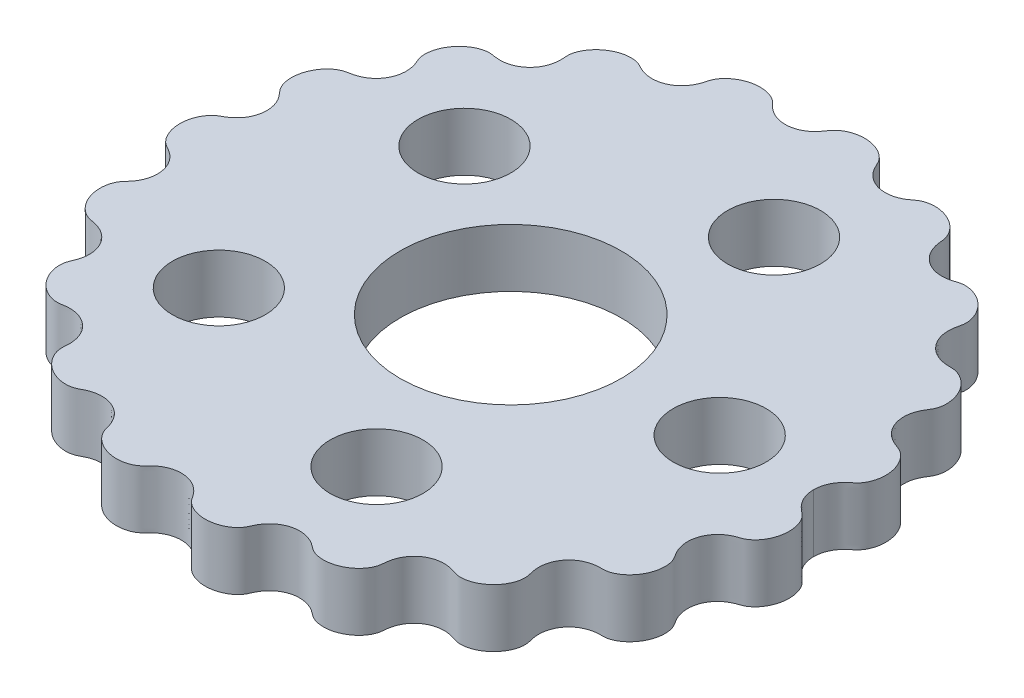
SolidWorks part; units mm, degrees
ref_plane "Front Plane" through (0, 0, 0) normal (0, 0, 1) x (1, 0, 0)
ref_plane "Top Plane" through (0, 0, 0) normal (0, 1, 0) x (1, 0, 0)
ref_plane "Right Plane" through (0, 0, 0) normal (1, 0, 0) x (0, 0, -1)
sketch "Sketch1" plane through (0, 0, 0) normal (0, 1, 0) x (1, 0, 0)
  line L0 (-28.5, 0) -> (26.1, 0) construction
  line L1 (0, 0) -> (-1.2, 0) construction
  line L2 (-1.2, -26.2965) -> (-1.2, 26.2965) construction
  line L3 (0, -27.4748) -> (0, 27.4748) construction
  line L4 (18, 0) -> (16.8, 0)
  line L5 (-1.2, 0) -> (-2.4, 0)
  circle A6 centre (0, 0) radius 9.525
  circle A7 centre (0, 0) radius 18
  circle A8 centre (18, 0) radius 4
  circle A9 centre (5.5623, -17.119) radius 4
  circle A10 centre (-14.5623, -10.5801) radius 4
  circle A11 centre (-14.5623, 10.5801) radius 4
  circle A12 centre (5.5623, 17.119) radius 4
  circle A13 centre (-1.2, 0) radius 30
  circle A14 centre (28.8, 0) radius 2.5
  circle A15 centre (27.3317, -9.2705) radius 2.5
  circle A16 centre (23.0705, -17.6336) radius 2.5
  circle A17 centre (16.4336, -24.2705) radius 2.5
  circle A18 centre (8.0705, -28.5317) radius 2.5
  circle A19 centre (-1.2, -30) radius 2.5
  circle A20 centre (-10.4705, -28.5317) radius 2.5
  circle A21 centre (-18.8336, -24.2705) radius 2.5
  circle A22 centre (-25.4705, -17.6336) radius 2.5
  circle A23 centre (-29.7317, -9.2705) radius 2.5
  circle A24 centre (-31.2, 0) radius 2.5
  circle A25 centre (-29.7317, 9.2705) radius 2.5
  circle A26 centre (-25.4705, 17.6336) radius 2.5
  circle A27 centre (-18.8336, 24.2705) radius 2.5
  circle A28 centre (-10.4705, 28.5317) radius 2.5
  circle A29 centre (-1.2, 30) radius 2.5
  circle A30 centre (8.0705, 28.5317) radius 2.5
  circle A31 centre (16.4336, 24.2705) radius 2.5
  circle A32 centre (23.0705, 17.6336) radius 2.5
  circle A33 centre (27.3317, 9.2705) radius 2.5
  circle A34 centre (-2.4, 0) radius 9.525
  circle A35 centre (-2.4, 0) radius 18
  circle A36 centre (15.6, 0) radius 4
  circle A37 centre (3.1623, -17.119) radius 4
  circle A38 centre (-16.9623, -10.5801) radius 4
  circle A39 centre (-16.9623, 10.5801) radius 4
  circle A40 centre (3.1623, 17.119) radius 4
  spline S0 degree 4 poles (26.9104, 6.6012) (26.9742, 6.5637) (27.0975, 6.4823) (27.3266, 6.2942) (27.6183, 5.9575) (27.8831, 5.5093) (28.0722, 4.9735) (28.1608, 4.4391) (28.1609, 3.9238) (28.093, 3.5007) (27.9838, 3.1507) (27.8591, 2.8784) (27.741, 2.6778) (27.605, 2.4959) (27.4503, 2.337) (27.2759, 2.2009) (27.1019, 2.0648) (26.9367, 1.9177) (26.7821, 1.7596) (26.65, 1.601) (26.5385, 1.4453) (26.4457, 1.295) (26.3692, 1.1524) (26.3017, 1.0053) (26.2435, 0.8544) (26.1947, 0.7002) (26.1557, 0.5423) (26.1271, 0.3877) (26.1084, 0.2314) (26.0989, 0.0495) (26.0994, -0.0671) (26.1108, -0.2691) (26.1342, -0.4315) (26.1693, -0.6042) (26.2157, -0.7717) (26.2733, -0.9361) (26.3418, -1.0961) (26.4279, -1.2656) (26.5348, -1.4419) (26.6997, -1.6703) (26.9014, -1.8899) (27.1248, -2.087) (27.3628, -2.2652) (27.5417, -2.4229) (27.6968, -2.6125) (27.831, -2.8239) (27.9427, -3.0552) (28.032, -3.3021) (28.1133, -3.6202) (28.1642, -4.0114) (28.1582, -4.4659) (28.0687, -4.972) (27.9224, -5.3919) (27.7522, -5.7264) (27.5792, -5.9861) (27.4226, -6.1811) (27.2087, -6.3966) (26.9704, -6.5815) (26.7043, -6.7144) (26.4261, -6.8021) (26.2084, -6.8853) (25.996, -6.9818) (25.7924, -7.0957) (25.5065, -7.2884) (25.1668, -7.5959) (24.8233, -8.0656) (24.5731, -8.7228) (24.5132, -9.3741) (24.5959, -9.9089) (24.7329, -10.3062) (24.8635, -10.5783) (24.9836, -10.7878) (25.1181, -10.988) (25.2439, -11.1944) (25.336, -11.4251) (25.3995, -11.6707) (25.4343, -11.9282) (25.442, -12.1937) (25.4188, -12.5249) (25.3424, -12.9166) (25.1912, -13.3478) (24.9449, -13.7987) (24.6361, -14.1974) (24.3194, -14.493) (24.0146, -14.7042) (23.7442, -14.8441) (23.522, -14.9308) (23.2952, -14.9909) (23.0662, -15.0181) (22.8362, -15.0154) (22.6065, -15.0188) (22.3771, -15.0374) (22.15, -15.0735) (21.9017, -15.1343) (21.6364, -15.2275) (21.2852, -15.3974) (20.867, -15.6962) (20.4577, -16.1544) (20.1676, -16.7441) (20.0407, -17.3441) (20.0443, -17.8376) (20.1013, -18.2083) (20.1783, -18.5102) (20.2374, -18.7529) (20.2542, -19.0071) (20.2367, -19.2645) (20.1753, -19.5877) (20.0454, -19.9662) (19.8257, -20.3791) (19.5033, -20.7922) (19.1257, -21.1406) (18.7061, -21.4192) (18.3126, -21.5978) (17.9573, -21.7007) (17.6591, -21.7472) (17.425, -21.7593) (17.197, -21.746) (16.9781, -21.7045) (16.7675, -21.6331) (16.5576, -21.5612) (16.3432, -21.5027) (16.1253, -21.4593) (15.7965, -21.4204) (15.3549, -21.428) (14.789, -21.5503) (14.1546, -21.8806) (13.6662, -22.3459) (13.3364, -22.8823) (13.1735, -23.3537) (13.1046, -23.717) (13.0767, -24.0228) (13.0578, -24.2682) (12.9987, -24.5141) (12.9032, -24.7542) (12.7442, -25.0453) (12.499, -25.369) (12.1557, -25.6963) (11.7049, -25.9946) (11.2116, -26.2122) (10.69, -26.3437) (10.2213, -26.3776) (9.8206, -26.3426) (9.499, -26.2667) (9.2556, -26.1771) (9.0298, -26.0566) (8.8316, -25.9026) (8.5839, -25.7111) (8.2645, -25.511) (7.8101, -25.3123) (7.2055, -25.1928) (6.5502, -25.2287) (5.9713, -25.4243) (5.5369, -25.6878) (5.2457, -25.9387) (5.0554, -26.1438) (4.8999, -26.3482) (4.7746, -26.5455) (4.6646, -26.7519) (4.569, -26.9649) (4.4763, -27.1796) (4.3535, -27.3793) (4.2033, -27.5619) (4.0321, -27.728) (3.7953, -27.9145) (3.4825, -28.1028) (3.0896, -28.2688) (2.605, -28.3883) (2.0954, -28.4312) (1.5735, -28.39) (1.1195, -28.2728) (0.7516, -28.1124) (0.4728, -27.9399) (0.2735, -27.7809) (0.1002, -27.6012) (-0.0369, -27.4007) (-0.1676, -27.1967) (-0.3131, -27.0024) (-0.5125, -26.7738) (-0.8252, -26.4899) (-1.2868, -26.2024) (-1.9065, -26.0034) (-2.5994, -25.9754) (-3.1568, -26.101) (-3.5653, -26.2832) (-3.8534, -26.4638) (-4.0409, -26.6046) (-4.2161, -26.7602) (-4.3804, -26.9272) (-4.5356, -27.1027) (-4.708, -27.2621) (-4.9066, -27.3955) (-5.1223, -27.5066) (-5.3531, -27.5948) (-5.5951, -27.6608) (-5.9041, -27.715) (-6.2804, -27.7366) (-6.7242, -27.7014) (-7.2225, -27.58) (-7.6392, -27.4035) (-7.9745, -27.2016) (-8.2316, -27.0015) (-8.4208, -26.8224) (-8.5884, -26.628) (-8.73, -26.4192) (-8.8438, -26.1979) (-8.9181, -25.9651) (-8.9731, -25.7277) (-9.0439, -25.4943) (-9.1531, -25.2096) (-9.3068, -24.9159) (-9.5135, -24.6237) (-9.8398, -24.2849) (-10.2644, -23.9778) (-10.8297, -23.7381) (-11.4105, -23.6609) (-11.8763, -23.6964) (-12.2188, -23.7735) (-12.4447, -23.8451) (-12.6638, -23.9353) (-12.8761, -24.0403) (-13.082, -24.1572) (-13.2986, -24.2543) (-13.5339, -24.3178) (-13.7805, -24.3538) (-14.0358, -24.3616) (-14.2964, -24.3431) (-14.6185, -24.2887) (-14.9949, -24.1775) (-15.4086, -23.9883) (-15.8372, -23.7006) (-16.1649, -23.3939) (-16.4043, -23.0978) (-16.5733, -22.8298) (-16.6877, -22.6036) (-16.7767, -22.3723) (-16.8377, -22.1385) (-16.8702, -21.9045) (-16.8664, -21.6745) (-16.8432, -21.4462) (-16.8326, -21.2169) (-16.8373, -20.9873) (-16.8603, -20.7588) (-16.9233, -20.4192) (-17.0718, -19.9806) (-17.369, -19.4772) (-17.8749, -18.9885) (-18.448, -18.6772) (-19.0275, -18.5257) (-19.5101, -18.5038) (-19.8766, -18.5383) (-20.1776, -18.5934) (-20.4214, -18.6224) (-20.6712, -18.6091) (-20.9209, -18.565) (-21.1679, -18.4906) (-21.4096, -18.39) (-21.6982, -18.2354) (-22.0201, -18.0093) (-22.351, -17.6983) (-22.6637, -17.2907) (-22.9048, -16.8434) (-23.0478, -16.4273) (-23.1163, -16.0571) (-23.132, -15.7508) (-23.1187, -15.5137) (-23.0797, -15.2858) (-23.0107, -15.072) (-22.918, -14.8679) (-22.8318, -14.6612) (-22.759, -14.4492) (-22.7023, -14.2323) (-22.658, -13.9823) (-22.6359, -13.6994) (-22.6507, -13.3001) (-22.7619, -12.7838) (-23.0293, -12.2149) (-23.4676, -11.712) (-23.9234, -11.3981) (-24.3155, -11.223) (-24.6094, -11.1314) (-24.8495, -11.076) (-25.0926, -11.0387) (-25.3345, -10.9908) (-25.5693, -10.9005) (-25.7937, -10.7797) (-26.006, -10.6307) (-26.2044, -10.4578) (-26.4303, -10.2184) (-26.6648, -9.8998) (-26.879, -9.4996) (-27.0444, -9.0157) (-27.13, -8.5201) (-27.1345, -8.0871) (-27.0849, -7.7198) (-27.006, -7.4259) (-26.9204, -7.2033) (-26.8122, -6.9952) (-26.6786, -6.8073) (-26.5213, -6.6394) (-26.3676, -6.4686) (-26.2255, -6.2877) (-26.0974, -6.0966) (-25.9747, -5.8762) (-25.8647, -5.6245) (-25.7524, -5.2647) (-25.6818, -4.7626) (-25.731, -4.1469) (-25.9619, -3.524) (-26.3213, -3.0106) (-26.6902, -2.673) (-27.001, -2.4627) (-27.2749, -2.314) (-27.4942, -2.1942) (-27.6938, -2.0358) (-27.8724, -1.8494) (-28.0299, -1.6395) (-28.1658, -1.4106) (-28.2784, -1.1691) (-28.3569, -0.9499) (-28.4099, -0.7574) (-28.4448, -0.5945) (-28.4671, -0.4646) (-28.4838, -0.3341) (-28.4949, -0.1942) (-28.5004, -0.0525) (-28.5005, 0.0456) (-28.4955, 0.1802) (-28.4857, 0.3127) (-28.4674, 0.4669) (-28.4356, 0.6491) (-28.3841, 0.8627) (-28.3055, 1.0987) (-28.2068, 1.3282) (-28.0876, 1.5473) (-27.9509, 1.7495) (-27.7973, 1.9316) (-27.6281, 2.0918) (-27.4431, 2.2241) (-27.2427, 2.3305) (-27.0445, 2.4404) (-26.8537, 2.5632) (-26.6725, 2.6998) (-26.4853, 2.8663) (-26.2987, 3.0673) (-26.073, 3.3712) (-25.8526, 3.7999) (-25.7033, 4.3429) (-25.6908, 4.9349) (-25.7972, 5.4631) (-25.983, 5.9142) (-26.1842, 6.2409) (-26.3898, 6.4964) (-26.5384, 6.6564) (-26.611, 6.7378) (-26.647, 6.7788) knots 0 0 0 0 0 0.002514 0.005029 0.010058 0.015086 0.020115 0.024264 0.028413 0.032562 0.034636 0.03671 0.038591 0.040472 0.042353 0.044234 0.046115 0.047995 0.049876 0.051757 0.053134 0.05451 0.055887 0.057263 0.05864 0.060016 0.061393 0.06277 0.064064 0.065358 0.066839 0.06832 0.069801 0.071282 0.072763 0.074244 0.075725 0.077206 0.079231 0.081256 0.085305 0.087329 0.089354 0.091379 0.093403 0.095635 0.097867 0.100099 0.102331 0.106795 0.111259 0.115506 0.119752 0.121875 0.123998 0.126122 0.128245 0.132212 0.134196 0.13618 0.138163 0.140147 0.142131 0.144114 0.149889 0.155664 0.161717 0.167769 0.171876 0.173929 0.175982 0.178036 0.180089 0.182142 0.184196 0.186453 0.18871 0.190968 0.193225 0.19774 0.202255 0.20645 0.210645 0.21484 0.216937 0.219035 0.220991 0.222947 0.224903 0.226859 0.228815 0.230771 0.232727 0.234683 0.237505 0.240328 0.245974 0.252074 0.258174 0.262418 0.266663 0.268785 0.270907 0.27303 0.275152 0.277414 0.279676 0.284201 0.288725 0.29325 0.297435 0.301619 0.305804 0.307896 0.309989 0.311878 0.313768 0.315658 0.317547 0.319437 0.321327 0.323216 0.325106 0.330698 0.336289 0.342722 0.349154 0.353338 0.357522 0.359614 0.361706 0.363798 0.365889 0.368184 0.370478 0.375067 0.379656 0.384245 0.388791 0.393338 0.397884 0.400157 0.40243 0.404563 0.406695 0.408827 0.41096 0.415225 0.41949 0.425619 0.431749 0.437282 0.440049 0.442815 0.444803 0.446791 0.448779 0.450767 0.452755 0.454743 0.456731 0.458718 0.460784 0.462849 0.466979 0.47111 0.47524 0.479777 0.484314 0.488851 0.491119 0.493388 0.495451 0.497514 0.499578 0.501641 0.503704 0.505768 0.509894 0.515977 0.52206 0.527644 0.533228 0.535221 0.537214 0.539208 0.541201 0.543194 0.545187 0.54718 0.549173 0.551306 0.553439 0.555572 0.557704 0.56197 0.566236 0.570665 0.575094 0.577308 0.579523 0.581737 0.583952 0.586026 0.5881 0.590174 0.592248 0.594322 0.596397 0.600545 0.6035 0.606456 0.612367 0.618261 0.624154 0.626169 0.628184 0.630198 0.632213 0.634228 0.636243 0.638257 0.640272 0.642493 0.644714 0.646935 0.649156 0.653597 0.658039 0.662348 0.666657 0.668812 0.670967 0.673121 0.675276 0.677229 0.679181 0.681134 0.683087 0.68504 0.686993 0.688946 0.690899 0.696786 0.702673 0.708614 0.714556 0.718724 0.722892 0.724976 0.72706 0.729144 0.731229 0.733454 0.73568 0.737906 0.740131 0.744583 0.749034 0.753293 0.757552 0.76181 0.76394 0.766069 0.767975 0.769882 0.771788 0.773694 0.775601 0.777507 0.779413 0.78132 0.784235 0.787151 0.792981 0.799177 0.805373 0.809561 0.811656 0.81375 0.815844 0.817939 0.820033 0.822127 0.824365 0.826603 0.828841 0.831079 0.835554 0.84003 0.844223 0.848415 0.852608 0.854705 0.856801 0.858757 0.860713 0.862669 0.864625 0.866581 0.868537 0.870493 0.87245 0.875161 0.877872 0.883295 0.889615 0.895936 0.900182 0.904428 0.906551 0.908674 0.910797 0.912919 0.915183 0.917446 0.919709 0.921972 0.924235 0.925367 0.926498 0.92763 0.928762 0.929893 0.931025 0.932085 0.933146 0.934206 0.935267 0.937388 0.939509 0.94163 0.943751 0.945872 0.947993 0.949922 0.951852 0.953781 0.95571 0.95764 0.959569 0.961498 0.963428 0.966159 0.968891 0.974355 0.979745 0.985135 0.988851 0.992568 0.996284 0.998142 1 1 1 1 1 construction
  spline S1 degree 4 poles (26.1, 0) (26.1, -0.0377) (26.102, -0.1127) (26.1108, -0.2691) (26.1342, -0.4315) (26.1693, -0.6042) (26.2157, -0.7717) (26.2733, -0.9361) (26.3418, -1.0961) (26.4279, -1.2656) (26.5348, -1.4419) (26.6997, -1.6703) (26.9014, -1.8899) (27.1248, -2.087) (27.3628, -2.2652) (27.5417, -2.4229) (27.6968, -2.6125) (27.831, -2.8239) (27.9427, -3.0552) (28.032, -3.3021) (28.1133, -3.6202) (28.1642, -4.0114) (28.1582, -4.4659) (28.0687, -4.972) (27.9224, -5.3919) (27.7522, -5.7264) (27.5792, -5.9861) (27.4226, -6.1811) (27.2087, -6.3966) (26.9704, -6.5815) (26.7043, -6.7144) (26.4261, -6.8021) (26.2084, -6.8853) (25.996, -6.9818) (25.7924, -7.0957) (25.5065, -7.2884) (25.1668, -7.5959) (24.8233, -8.0656) (24.5731, -8.7228) (24.5132, -9.3741) (24.5959, -9.9089) (24.7329, -10.3062) (24.8635, -10.5783) (24.9836, -10.7878) (25.1181, -10.988) (25.2439, -11.1944) (25.336, -11.4251) (25.3995, -11.6707) (25.4343, -11.9282) (25.442, -12.1937) (25.4188, -12.5249) (25.3424, -12.9166) (25.1912, -13.3478) (24.9449, -13.7987) (24.6361, -14.1974) (24.3194, -14.493) (24.0146, -14.7042) (23.7442, -14.8441) (23.522, -14.9308) (23.2952, -14.9909) (23.0662, -15.0181) (22.8362, -15.0154) (22.6065, -15.0188) (22.3771, -15.0374) (22.15, -15.0735) (21.9017, -15.1343) (21.6364, -15.2275) (21.2852, -15.3974) (20.867, -15.6962) (20.4577, -16.1544) (20.1676, -16.7441) (20.0407, -17.3441) (20.0443, -17.8376) (20.1013, -18.2083) (20.1783, -18.5102) (20.2374, -18.7529) (20.2542, -19.0071) (20.2367, -19.2645) (20.1753, -19.5877) (20.0454, -19.9662) (19.8257, -20.3791) (19.5033, -20.7922) (19.1257, -21.1406) (18.7061, -21.4192) (18.3126, -21.5978) (17.9573, -21.7007) (17.6591, -21.7472) (17.425, -21.7593) (17.197, -21.746) (16.9781, -21.7045) (16.7675, -21.6331) (16.5576, -21.5612) (16.3432, -21.5027) (16.1253, -21.4593) (15.7965, -21.4204) (15.3549, -21.428) (14.789, -21.5503) (14.1546, -21.8806) (13.6662, -22.3459) (13.3364, -22.8823) (13.1735, -23.3537) (13.1046, -23.717) (13.0767, -24.0228) (13.0578, -24.2682) (12.9987, -24.5141) (12.9032, -24.7542) (12.7442, -25.0453) (12.499, -25.369) (12.1557, -25.6963) (11.7049, -25.9946) (11.2116, -26.2122) (10.69, -26.3437) (10.2213, -26.3776) (9.8206, -26.3426) (9.499, -26.2667) (9.2556, -26.1771) (9.0298, -26.0566) (8.8316, -25.9026) (8.5839, -25.7111) (8.2645, -25.511) (7.8101, -25.3123) (7.2055, -25.1928) (6.5502, -25.2287) (5.9713, -25.4243) (5.5369, -25.6878) (5.2457, -25.9387) (5.0554, -26.1438) (4.8999, -26.3482) (4.7746, -26.5455) (4.6646, -26.7519) (4.569, -26.9649) (4.4763, -27.1796) (4.3535, -27.3793) (4.2033, -27.5619) (4.0321, -27.728) (3.7953, -27.9145) (3.4825, -28.1028) (3.0896, -28.2688) (2.605, -28.3883) (2.0954, -28.4312) (1.5735, -28.39) (1.1195, -28.2728) (0.7516, -28.1124) (0.4728, -27.9399) (0.2735, -27.7809) (0.1002, -27.6012) (-0.0369, -27.4007) (-0.1676, -27.1967) (-0.3131, -27.0024) (-0.5125, -26.7738) (-0.8252, -26.4899) (-1.2868, -26.2024) (-1.9065, -26.0034) (-2.5994, -25.9754) (-3.1568, -26.101) (-3.5653, -26.2832) (-3.8534, -26.4638) (-4.0409, -26.6046) (-4.2161, -26.7602) (-4.3804, -26.9272) (-4.5356, -27.1027) (-4.708, -27.2621) (-4.9066, -27.3955) (-5.1223, -27.5066) (-5.3531, -27.5948) (-5.5951, -27.6608) (-5.9041, -27.715) (-6.2804, -27.7366) (-6.7242, -27.7014) (-7.2225, -27.58) (-7.6392, -27.4035) (-7.9745, -27.2016) (-8.2316, -27.0015) (-8.4208, -26.8224) (-8.5884, -26.628) (-8.73, -26.4192) (-8.8438, -26.1979) (-8.9181, -25.9651) (-8.9731, -25.7277) (-9.0439, -25.4943) (-9.1531, -25.2096) (-9.3068, -24.9159) (-9.5135, -24.6237) (-9.8398, -24.2849) (-10.2644, -23.9778) (-10.8297, -23.7381) (-11.4105, -23.6609) (-11.8763, -23.6964) (-12.2188, -23.7735) (-12.4447, -23.8451) (-12.6638, -23.9353) (-12.8761, -24.0403) (-13.082, -24.1572) (-13.2986, -24.2543) (-13.5339, -24.3178) (-13.7805, -24.3538) (-14.0358, -24.3616) (-14.2964, -24.3431) (-14.6185, -24.2887) (-14.9949, -24.1775) (-15.4086, -23.9883) (-15.8372, -23.7006) (-16.1649, -23.3939) (-16.4043, -23.0978) (-16.5733, -22.8298) (-16.6877, -22.6036) (-16.7767, -22.3723) (-16.8377, -22.1385) (-16.8702, -21.9045) (-16.8664, -21.6745) (-16.8432, -21.4462) (-16.8326, -21.2169) (-16.8373, -20.9873) (-16.8603, -20.7588) (-16.9233, -20.4192) (-17.0718, -19.9806) (-17.369, -19.4772) (-17.8749, -18.9885) (-18.448, -18.6772) (-19.0275, -18.5257) (-19.5101, -18.5038) (-19.8766, -18.5383) (-20.1776, -18.5934) (-20.4214, -18.6224) (-20.6712, -18.6091) (-20.9209, -18.565) (-21.1679, -18.4906) (-21.4096, -18.39) (-21.6982, -18.2354) (-22.0201, -18.0093) (-22.351, -17.6983) (-22.6637, -17.2907) (-22.9048, -16.8434) (-23.0478, -16.4273) (-23.1163, -16.0571) (-23.132, -15.7508) (-23.1187, -15.5137) (-23.0797, -15.2858) (-23.0107, -15.072) (-22.918, -14.8679) (-22.8318, -14.6612) (-22.759, -14.4492) (-22.7023, -14.2323) (-22.658, -13.9823) (-22.6359, -13.6994) (-22.6507, -13.3001) (-22.7619, -12.7838) (-23.0293, -12.2149) (-23.4676, -11.712) (-23.9234, -11.3981) (-24.3155, -11.223) (-24.6094, -11.1314) (-24.8495, -11.076) (-25.0926, -11.0387) (-25.3345, -10.9908) (-25.5693, -10.9005) (-25.7937, -10.7797) (-26.006, -10.6307) (-26.2044, -10.4578) (-26.4303, -10.2184) (-26.6648, -9.8998) (-26.879, -9.4996) (-27.0444, -9.0157) (-27.13, -8.5201) (-27.1345, -8.0871) (-27.0849, -7.7198) (-27.006, -7.4259) (-26.9204, -7.2033) (-26.8122, -6.9952) (-26.6786, -6.8073) (-26.5213, -6.6394) (-26.3676, -6.4686) (-26.2255, -6.2877) (-26.0974, -6.0966) (-25.9747, -5.8762) (-25.8647, -5.6245) (-25.7524, -5.2647) (-25.6818, -4.7626) (-25.731, -4.1469) (-25.9619, -3.524) (-26.3213, -3.0106) (-26.6902, -2.673) (-27.001, -2.4627) (-27.2749, -2.314) (-27.4942, -2.1942) (-27.6938, -2.0358) (-27.8724, -1.8494) (-28.0299, -1.6395) (-28.1658, -1.4106) (-28.2784, -1.1691) (-28.3569, -0.9499) (-28.4099, -0.7574) (-28.4448, -0.5945) (-28.4671, -0.4646) (-28.4838, -0.3341) (-28.4949, -0.1942) (-28.4991, -0.0862) (-28.5, -0.0288) (-28.5, 0) knots 0.065358 0.065358 0.065358 0.065358 0.065358 0.066839 0.06832 0.069801 0.071282 0.072763 0.074244 0.075725 0.077206 0.079231 0.081256 0.085305 0.087329 0.089354 0.091379 0.093403 0.095635 0.097867 0.100099 0.102331 0.106795 0.111259 0.115506 0.119752 0.121875 0.123998 0.126122 0.128245 0.132212 0.134196 0.13618 0.138163 0.140147 0.142131 0.144114 0.149889 0.155664 0.161717 0.167769 0.171876 0.173929 0.175982 0.178036 0.180089 0.182142 0.184196 0.186453 0.18871 0.190968 0.193225 0.19774 0.202255 0.20645 0.210645 0.21484 0.216937 0.219035 0.220991 0.222947 0.224903 0.226859 0.228815 0.230771 0.232727 0.234683 0.237505 0.240328 0.245974 0.252074 0.258174 0.262418 0.266663 0.268785 0.270907 0.27303 0.275152 0.277414 0.279676 0.284201 0.288725 0.29325 0.297435 0.301619 0.305804 0.307896 0.309989 0.311878 0.313768 0.315658 0.317547 0.319437 0.321327 0.323216 0.325106 0.330698 0.336289 0.342722 0.349154 0.353338 0.357522 0.359614 0.361706 0.363798 0.365889 0.368184 0.370478 0.375067 0.379656 0.384245 0.388791 0.393338 0.397884 0.400157 0.40243 0.404563 0.406695 0.408827 0.41096 0.415225 0.41949 0.425619 0.431749 0.437282 0.440049 0.442815 0.444803 0.446791 0.448779 0.450767 0.452755 0.454743 0.456731 0.458718 0.460784 0.462849 0.466979 0.47111 0.47524 0.479777 0.484314 0.488851 0.491119 0.493388 0.495451 0.497514 0.499578 0.501641 0.503704 0.505768 0.509894 0.515977 0.52206 0.527644 0.533228 0.535221 0.537214 0.539208 0.541201 0.543194 0.545187 0.54718 0.549173 0.551306 0.553439 0.555572 0.557704 0.56197 0.566236 0.570665 0.575094 0.577308 0.579523 0.581737 0.583952 0.586026 0.5881 0.590174 0.592248 0.594322 0.596397 0.600545 0.6035 0.606456 0.612367 0.618261 0.624154 0.626169 0.628184 0.630198 0.632213 0.634228 0.636243 0.638257 0.640272 0.642493 0.644714 0.646935 0.649156 0.653597 0.658039 0.662348 0.666657 0.668812 0.670967 0.673121 0.675276 0.677229 0.679181 0.681134 0.683087 0.68504 0.686993 0.688946 0.690899 0.696786 0.702673 0.708614 0.714556 0.718724 0.722892 0.724976 0.72706 0.729144 0.731229 0.733454 0.73568 0.737906 0.740131 0.744583 0.749034 0.753293 0.757552 0.76181 0.76394 0.766069 0.767975 0.769882 0.771788 0.773694 0.775601 0.777507 0.779413 0.78132 0.784235 0.787151 0.792981 0.799177 0.805373 0.809561 0.811656 0.81375 0.815844 0.817939 0.820033 0.822127 0.824365 0.826603 0.828841 0.831079 0.835554 0.84003 0.844223 0.848415 0.852608 0.854705 0.856801 0.858757 0.860713 0.862669 0.864625 0.866581 0.868537 0.870493 0.87245 0.875161 0.877872 0.883295 0.889615 0.895936 0.900182 0.904428 0.906551 0.908674 0.910797 0.912919 0.915183 0.917446 0.919709 0.921972 0.924235 0.925367 0.926498 0.92763 0.928762 0.929893 0.931025 0.931025 0.931025 0.931025 0.931025
  spline S2 degree 4 poles (26.1, 0) (26.1, 0.0376) (26.102, 0.1124) (26.1108, 0.2685) (26.1342, 0.4303) (26.1693, 0.6027) (26.2157, 0.7697) (26.2733, 0.9336) (26.3417, 1.0932) (26.4279, 1.2622) (26.5346, 1.438) (26.6647, 1.6175) (26.8202, 1.7972) (26.9901, 1.9633) (27.1709, 2.1172) (27.3596, 2.2614) (27.5347, 2.4225) (27.6873, 2.6133) (27.8194, 2.8254) (27.9294, 3.0568) (28.0174, 3.3035) (28.0973, 3.6212) (28.1472, 4.0116) (28.1407, 4.4663) (28.0507, 4.9735) (27.8829, 5.455) (27.6715, 5.843) (27.4436, 6.1449) (27.2267, 6.3648) (27.0409, 6.5166) (26.8436, 6.6432) (26.6359, 6.7382) (26.4199, 6.8111) (26.2069, 6.8919) (25.9995, 6.9866) (25.7999, 7.097) (25.5146, 7.2869) (25.172, 7.593) (24.8251, 8.0632) (24.573, 8.723) (24.5135, 9.3751) (24.5967, 9.9085) (24.7339, 10.3046) (24.8642, 10.5762) (24.9838, 10.7853) (25.1166, 10.986) (25.2378, 11.1945) (25.3267, 11.4258) (25.3878, 11.6713) (25.4209, 11.9285) (25.4273, 12.1933) (25.4029, 12.5237) (25.3257, 12.9142) (25.174, 13.3453) (24.9269, 13.7973) (24.6164, 14.1978) (24.297, 14.4955) (23.9896, 14.7081) (23.7185, 14.8479) (23.4979, 14.934) (23.2747, 14.9937) (23.0513, 15.0227) (22.8265, 15.0238) (22.6021, 15.0278) (22.378, 15.046) (22.1559, 15.0804) (21.8286, 15.1585) (21.4093, 15.3223) (20.9247, 15.6352) (20.4568, 16.1578) (20.1669, 16.7485) (20.041, 17.3471) (20.0453, 17.8394) (20.1023, 18.2092) (20.1778, 18.5107) (20.2318, 18.7541) (20.2449, 19.0078) (20.2252, 19.2644) (20.1746, 19.5212) (20.0962, 19.7748) (19.9675, 20.0808) (19.7692, 20.427) (19.4884, 20.786) (19.1123, 21.133) (18.6951, 21.411) (18.3044, 21.5899) (17.9516, 21.6944) (17.5971, 21.7522) (17.3027, 21.7613) (17.0135, 21.7242) (16.7419, 21.6352) (16.5255, 21.5634) (16.3045, 21.5051) (16.08, 21.4631) (15.8308, 21.4372) (15.5583, 21.4348) (15.1861, 21.4722) (14.6961, 21.6037) (14.1458, 21.8923) (13.6634, 22.3528) (13.3351, 22.8883) (13.1733, 23.3588) (13.1047, 23.7212) (13.0759, 24.0263) (13.0525, 24.2707) (12.9895, 24.515) (12.8921, 24.7535) (12.7313, 25.0427) (12.4854, 25.3645) (12.1419, 25.6899) (11.6909, 25.9876) (11.1964, 26.2054) (10.6723, 26.3373) (10.2003, 26.3711) (9.7968, 26.3356) (9.4748, 26.2593) (9.233, 26.1706) (9.01, 26.0529) (8.8137, 25.9055) (8.5704, 25.7195) (8.2582, 25.5237) (7.8094, 25.325) (7.2073, 25.202) (6.5461, 25.2353) (5.8772, 25.4622) (5.3986, 25.786) (5.085, 26.1055) (4.8853, 26.3742) (4.7666, 26.5637) (4.6617, 26.7612) (4.5693, 26.9645) (4.4773, 27.1684) (4.3594, 27.359) (4.2144, 27.5373) (4.0466, 27.7027) (3.8098, 27.8925) (3.4925, 28.0862) (3.093, 28.2569) (2.6024, 28.3789) (2.0891, 28.4226) (1.566, 28.382) (1.1127, 28.2662) (0.7451, 28.1078) (0.4658, 27.9376) (0.2655, 27.7808) (0.0903, 27.6039) (-0.0506, 27.4068) (-0.1822, 27.204) (-0.3275, 27.0102) (-0.5264, 26.7821) (-0.838, 26.4986) (-1.2981, 26.2111) (-1.9184, 26.0114) (-2.6145, 25.984) (-3.1735, 26.1125) (-3.582, 26.2979) (-3.8673, 26.4791) (-4.0499, 26.6174) (-4.2212, 26.7695) (-4.3819, 26.9324) (-4.5359, 27.1018) (-4.7063, 27.2554) (-4.9021, 27.3863) (-5.1165, 27.4966) (-5.3472, 27.5851) (-5.5911, 27.6519) (-5.9024, 27.7067) (-6.2817, 27.7289) (-6.73, 27.6934) (-7.2343, 27.5702) (-7.6563, 27.3905) (-7.9967, 27.1843) (-8.2563, 26.9795) (-8.4483, 26.7967) (-8.6511, 26.5554) (-8.817, 26.2938) (-8.9134, 26.0392) (-8.9701, 25.8124) (-9.0327, 25.5873) (-9.1257, 25.31) (-9.3159, 24.91) (-9.6747, 24.4361) (-10.1835, 24.0258) (-10.8362, 23.7471) (-11.4204, 23.6699) (-11.885, 23.7058) (-12.2267, 23.7831) (-12.452, 23.8548) (-12.6708, 23.9446) (-12.8827, 24.0491) (-13.0896, 24.1633) (-13.3076, 24.2559) (-13.543, 24.3166) (-13.7894, 24.3504) (-14.0442, 24.3567) (-14.3041, 24.337) (-14.6252, 24.2816) (-15.0005, 24.1698) (-15.413, 23.9806) (-15.8407, 23.6936) (-16.2143, 23.3448) (-16.485, 22.9926) (-16.6692, 22.6601) (-16.7825, 22.3711) (-16.8455, 22.1383) (-16.8805, 21.9053) (-16.8813, 21.6757) (-16.8608, 21.4476) (-16.8506, 21.2188) (-16.8554, 20.9897) (-16.8782, 20.7616) (-16.9407, 20.4228) (-17.0884, 19.9851) (-17.3858, 19.4807) (-17.8945, 18.9905) (-18.4699, 18.6811) (-18.9904, 18.5487) (-19.4065, 18.5188) (-19.706, 18.5311) (-19.9442, 18.558) (-20.1802, 18.5992) (-20.4191, 18.6236) (-20.6652, 18.6099) (-20.9131, 18.5657) (-21.1602, 18.4916) (-21.4036, 18.3903) (-21.6943, 18.2349) (-22.0185, 18.0074) (-22.3518, 17.6944) (-22.6668, 17.2838) (-22.9095, 16.8332) (-23.0533, 16.4139) (-23.122, 16.0408) (-23.1375, 15.7333) (-23.1242, 15.4968) (-23.0858, 15.2707) (-23.0198, 15.0593) (-22.9309, 14.8568) (-22.847, 14.6525) (-22.7758, 14.4431) (-22.7201, 14.2291) (-22.6612, 13.8972) (-22.6444, 13.4427) (-22.7419, 12.8653) (-23.0456, 12.2192) (-23.4424, 11.7647) (-23.8363, 11.4753) (-24.161, 11.3062) (-24.3884, 11.2127) (-24.6231, 11.1398) (-24.8625, 11.0843) (-25.1048, 11.0455) (-25.3451, 10.9926) (-25.5781, 10.8996) (-25.8009, 10.7771) (-26.0117, 10.6271) (-26.2088, 10.4536) (-26.4333, 10.2139) (-26.6665, 9.8956) (-26.8796, 9.4961) (-27.0447, 9.0134) (-27.1306, 8.5189) (-27.1361, 8.0869) (-27.0881, 7.7202) (-27.0111, 7.4265) (-26.9274, 7.2037) (-26.8215, 6.9951) (-26.6914, 6.8052) (-26.5372, 6.635) (-26.3844, 6.4641) (-26.2428, 6.2834) (-26.1149, 6.0928) (-25.9923, 5.8728) (-25.8823, 5.6218) (-25.77, 5.2629) (-25.699, 4.7597) (-25.7493, 4.1408) (-25.9834, 3.518) (-26.345, 3.0082) (-26.7118, 2.6756) (-27.016, 2.4701) (-27.2831, 2.3232) (-27.4957, 2.2024) (-27.6915, 2.0453) (-27.8687, 1.86) (-28.0262, 1.6502) (-28.1632, 1.4198) (-28.2767, 1.1768) (-28.3557, 0.9562) (-28.4092, 0.7624) (-28.4443, 0.5985) (-28.4668, 0.4676) (-28.4836, 0.3363) (-28.4949, 0.1958) (-28.4991, 0.0868) (-28.5, 0.029) (-28.5, 0) knots 0.065429 0.065429 0.065429 0.065429 0.065429 0.066909 0.06839 0.06987 0.071351 0.072832 0.074312 0.075793 0.077274 0.079299 0.081323 0.083348 0.085373 0.087398 0.089423 0.091448 0.093473 0.095705 0.097936 0.100168 0.1024 0.106864 0.111328 0.115615 0.119903 0.124191 0.126335 0.128478 0.130422 0.132365 0.134309 0.136252 0.138195 0.140139 0.142082 0.144026 0.149879 0.155733 0.161783 0.167834 0.17194 0.173994 0.176047 0.1781 0.180154 0.182207 0.184261 0.186518 0.188775 0.191032 0.193289 0.197803 0.202317 0.206554 0.210791 0.215028 0.217147 0.219265 0.221181 0.223096 0.225012 0.226928 0.228843 0.230759 0.232675 0.23459 0.240315 0.24604 0.252138 0.258236 0.26248 0.266724 0.268846 0.270968 0.273091 0.275213 0.277474 0.279736 0.281998 0.28426 0.288783 0.293307 0.297478 0.30165 0.305822 0.307907 0.309993 0.313887 0.315834 0.317781 0.319728 0.321675 0.323622 0.325569 0.328265 0.330961 0.336353 0.342782 0.349211 0.353395 0.357579 0.35967 0.361762 0.363854 0.365946 0.36824 0.370534 0.375121 0.379709 0.384296 0.388885 0.393473 0.398062 0.400356 0.40265 0.404741 0.406832 0.408922 0.411013 0.415194 0.419375 0.425582 0.43179 0.437484 0.443178 0.445084 0.44699 0.448896 0.450802 0.452707 0.454613 0.456519 0.458425 0.460533 0.46264 0.466855 0.471071 0.475286 0.479822 0.484358 0.488895 0.491163 0.493431 0.495494 0.497557 0.499621 0.501684 0.503747 0.505811 0.509937 0.516018 0.522099 0.527761 0.533424 0.535376 0.537328 0.539281 0.541233 0.543185 0.545137 0.547089 0.549041 0.551195 0.55335 0.555504 0.557658 0.561967 0.566275 0.570786 0.575296 0.577551 0.579806 0.582061 0.584316 0.588304 0.590297 0.591294 0.592291 0.596278 0.600266 0.606335 0.612404 0.618295 0.624187 0.626202 0.628218 0.630233 0.632248 0.634263 0.636278 0.638293 0.640308 0.642529 0.64475 0.646971 0.649191 0.653633 0.658074 0.662384 0.666693 0.671002 0.673157 0.675311 0.677265 0.679218 0.681171 0.683124 0.685077 0.68703 0.688983 0.690936 0.696822 0.702707 0.708727 0.714747 0.718834 0.720878 0.722922 0.724965 0.727009 0.729053 0.731096 0.733342 0.735588 0.737834 0.74008 0.744572 0.749064 0.753364 0.757665 0.761965 0.764115 0.766265 0.76815 0.770035 0.771919 0.773804 0.775689 0.777574 0.779458 0.781343 0.787178 0.793013 0.799206 0.805399 0.807494 0.809588 0.811682 0.813777 0.815871 0.817965 0.82006 0.822154 0.824391 0.826629 0.828866 0.831104 0.835579 0.840053 0.844247 0.84844 0.852634 0.854731 0.856827 0.858784 0.86074 0.862697 0.864654 0.86661 0.868567 0.870523 0.87248 0.875191 0.877902 0.883324 0.889723 0.896121 0.900285 0.904449 0.906531 0.908613 0.910695 0.912776 0.91506 0.917343 0.919626 0.92191 0.924193 0.925335 0.926476 0.927618 0.92876 0.929901 0.931043 0.931043 0.931043 0.931043 0.931043
  spline S3 degree 4 poles (-28.5, 0) (-28.5, -0.0377) (-28.502, -0.1127) (-28.5108, -0.2691) (-28.5342, -0.4315) (-28.5693, -0.6042) (-28.6157, -0.7717) (-28.6733, -0.9361) (-28.7418, -1.0961) (-28.8279, -1.2656) (-28.9348, -1.4419) (-29.0997, -1.6703) (-29.3014, -1.8899) (-29.5248, -2.087) (-29.7628, -2.2652) (-29.9417, -2.4229) (-30.0968, -2.6125) (-30.231, -2.8239) (-30.3427, -3.0552) (-30.432, -3.3021) (-30.5133, -3.6202) (-30.5642, -4.0114) (-30.5582, -4.4659) (-30.4687, -4.972) (-30.3224, -5.3919) (-30.1522, -5.7264) (-29.9792, -5.9861) (-29.8226, -6.1811) (-29.6087, -6.3966) (-29.3704, -6.5815) (-29.1043, -6.7144) (-28.8261, -6.8021) (-28.6084, -6.8853) (-28.396, -6.9818) (-28.1924, -7.0957) (-27.9065, -7.2884) (-27.5668, -7.5959) (-27.2233, -8.0656) (-26.9731, -8.7228) (-26.9132, -9.3741) (-26.9959, -9.9089) (-27.1329, -10.3062) (-27.2635, -10.5783) (-27.3836, -10.7878) (-27.5181, -10.988) (-27.6439, -11.1944) (-27.736, -11.4251) (-27.7995, -11.6707) (-27.8343, -11.9282) (-27.842, -12.1937) (-27.8188, -12.5249) (-27.7424, -12.9166) (-27.5912, -13.3478) (-27.3449, -13.7987) (-27.0361, -14.1974) (-26.7194, -14.493) (-26.4146, -14.7042) (-26.1442, -14.8441) (-25.922, -14.9308) (-25.6952, -14.9909) (-25.4662, -15.0181) (-25.2362, -15.0154) (-25.0065, -15.0188) (-24.7771, -15.0374) (-24.55, -15.0735) (-24.3017, -15.1343) (-24.0364, -15.2275) (-23.6852, -15.3974) (-23.267, -15.6962) (-22.8577, -16.1544) (-22.5676, -16.7441) (-22.4407, -17.3441) (-22.4443, -17.8376) (-22.5013, -18.2083) (-22.5783, -18.5102) (-22.6374, -18.7529) (-22.6542, -19.0071) (-22.6367, -19.2645) (-22.5753, -19.5877) (-22.4454, -19.9662) (-22.2257, -20.3791) (-21.9033, -20.7922) (-21.5257, -21.1406) (-21.1061, -21.4192) (-20.7126, -21.5978) (-20.3573, -21.7007) (-20.0591, -21.7472) (-19.825, -21.7593) (-19.597, -21.746) (-19.3781, -21.7045) (-19.1675, -21.6331) (-18.9576, -21.5612) (-18.7432, -21.5027) (-18.5253, -21.4593) (-18.1965, -21.4204) (-17.7549, -21.428) (-17.189, -21.5503) (-16.5546, -21.8806) (-16.0662, -22.3459) (-15.7364, -22.8823) (-15.5735, -23.3537) (-15.5046, -23.717) (-15.4767, -24.0228) (-15.4578, -24.2682) (-15.3987, -24.5141) (-15.3032, -24.7542) (-15.1442, -25.0453) (-14.899, -25.369) (-14.5557, -25.6963) (-14.1049, -25.9946) (-13.6116, -26.2122) (-13.09, -26.3437) (-12.6213, -26.3776) (-12.2206, -26.3426) (-11.899, -26.2667) (-11.6556, -26.1771) (-11.4298, -26.0566) (-11.2316, -25.9026) (-10.9839, -25.7111) (-10.6645, -25.511) (-10.2101, -25.3123) (-9.6055, -25.1928) (-8.9502, -25.2287) (-8.3713, -25.4243) (-7.9369, -25.6878) (-7.6457, -25.9387) (-7.4554, -26.1438) (-7.2999, -26.3482) (-7.1746, -26.5455) (-7.0646, -26.7519) (-6.969, -26.9649) (-6.8763, -27.1796) (-6.7535, -27.3793) (-6.6033, -27.5619) (-6.4321, -27.728) (-6.1953, -27.9145) (-5.8825, -28.1028) (-5.4896, -28.2688) (-5.005, -28.3883) (-4.4954, -28.4312) (-3.9735, -28.39) (-3.5195, -28.2728) (-3.1516, -28.1124) (-2.8728, -27.9399) (-2.6735, -27.7809) (-2.5002, -27.6012) (-2.3631, -27.4007) (-2.2324, -27.1967) (-2.0869, -27.0024) (-1.8875, -26.7738) (-1.5748, -26.4899) (-1.1132, -26.2024) (-0.4935, -26.0034) (0.1994, -25.9754) (0.7568, -26.101) (1.1653, -26.2832) (1.4534, -26.4638) (1.6409, -26.6046) (1.8161, -26.7602) (1.9804, -26.9272) (2.1356, -27.1027) (2.308, -27.2621) (2.5066, -27.3955) (2.7223, -27.5066) (2.9531, -27.5948) (3.1951, -27.6608) (3.5041, -27.715) (3.8804, -27.7366) (4.3242, -27.7014) (4.8225, -27.58) (5.2392, -27.4035) (5.5745, -27.2016) (5.8316, -27.0015) (6.0208, -26.8224) (6.1884, -26.628) (6.33, -26.4192) (6.4438, -26.1979) (6.5181, -25.9651) (6.5731, -25.7277) (6.6439, -25.4943) (6.7531, -25.2096) (6.9068, -24.9159) (7.1135, -24.6237) (7.4398, -24.2849) (7.8644, -23.9778) (8.4297, -23.7381) (9.0105, -23.6609) (9.4763, -23.6964) (9.8188, -23.7735) (10.0447, -23.8451) (10.2638, -23.9353) (10.4761, -24.0403) (10.682, -24.1572) (10.8986, -24.2543) (11.1339, -24.3178) (11.3805, -24.3538) (11.6358, -24.3616) (11.8964, -24.3431) (12.2185, -24.2887) (12.5949, -24.1775) (13.0086, -23.9883) (13.4372, -23.7006) (13.7649, -23.3939) (14.0043, -23.0978) (14.1733, -22.8298) (14.2877, -22.6036) (14.3767, -22.3723) (14.4377, -22.1385) (14.4702, -21.9045) (14.4664, -21.6745) (14.4432, -21.4462) (14.4326, -21.2169) (14.4373, -20.9873) (14.4603, -20.7588) (14.5233, -20.4192) (14.6718, -19.9806) (14.969, -19.4772) (15.4749, -18.9885) (16.048, -18.6772) (16.6275, -18.5257) (17.1101, -18.5038) (17.4766, -18.5383) (17.7776, -18.5934) (18.0214, -18.6224) (18.2712, -18.6091) (18.5209, -18.565) (18.7679, -18.4906) (19.0096, -18.39) (19.2982, -18.2354) (19.6201, -18.0093) (19.951, -17.6983) (20.2637, -17.2907) (20.5048, -16.8434) (20.6478, -16.4273) (20.7163, -16.0571) (20.732, -15.7508) (20.7187, -15.5137) (20.6797, -15.2858) (20.6107, -15.072) (20.518, -14.8679) (20.4318, -14.6612) (20.359, -14.4492) (20.3023, -14.2323) (20.258, -13.9823) (20.2359, -13.6994) (20.2507, -13.3001) (20.3619, -12.7838) (20.6293, -12.2149) (21.0676, -11.712) (21.5234, -11.3981) (21.9155, -11.223) (22.2094, -11.1314) (22.4495, -11.076) (22.6926, -11.0387) (22.9345, -10.9908) (23.1693, -10.9005) (23.3937, -10.7797) (23.606, -10.6307) (23.8044, -10.4578) (24.0303, -10.2184) (24.2648, -9.8998) (24.479, -9.4996) (24.6444, -9.0157) (24.73, -8.5201) (24.7345, -8.0871) (24.6849, -7.7198) (24.606, -7.4259) (24.5204, -7.2033) (24.4122, -6.9952) (24.2786, -6.8073) (24.1213, -6.6394) (23.9676, -6.4686) (23.8255, -6.2877) (23.6974, -6.0966) (23.5747, -5.8762) (23.4647, -5.6245) (23.3524, -5.2647) (23.2818, -4.7626) (23.331, -4.1469) (23.5619, -3.524) (23.9213, -3.0106) (24.2902, -2.673) (24.601, -2.4627) (24.8749, -2.314) (25.0942, -2.1942) (25.2938, -2.0358) (25.4724, -1.8494) (25.6299, -1.6395) (25.7658, -1.4106) (25.8784, -1.1691) (25.9569, -0.9499) (26.0099, -0.7574) (26.0448, -0.5945) (26.0671, -0.4646) (26.0838, -0.3341) (26.0949, -0.1942) (26.0991, -0.0862) (26.1, -0.0288) (26.1, 0) knots 0.065358 0.065358 0.065358 0.065358 0.065358 0.066839 0.06832 0.069801 0.071282 0.072763 0.074244 0.075725 0.077206 0.079231 0.081256 0.085305 0.087329 0.089354 0.091379 0.093403 0.095635 0.097867 0.100099 0.102331 0.106795 0.111259 0.115506 0.119752 0.121875 0.123998 0.126122 0.128245 0.132212 0.134196 0.13618 0.138163 0.140147 0.142131 0.144114 0.149889 0.155664 0.161717 0.167769 0.171876 0.173929 0.175982 0.178036 0.180089 0.182142 0.184196 0.186453 0.18871 0.190968 0.193225 0.19774 0.202255 0.20645 0.210645 0.21484 0.216937 0.219035 0.220991 0.222947 0.224903 0.226859 0.228815 0.230771 0.232727 0.234683 0.237505 0.240328 0.245974 0.252074 0.258174 0.262418 0.266663 0.268785 0.270907 0.27303 0.275152 0.277414 0.279676 0.284201 0.288725 0.29325 0.297435 0.301619 0.305804 0.307896 0.309989 0.311878 0.313768 0.315658 0.317547 0.319437 0.321327 0.323216 0.325106 0.330698 0.336289 0.342722 0.349154 0.353338 0.357522 0.359614 0.361706 0.363798 0.365889 0.368184 0.370478 0.375067 0.379656 0.384245 0.388791 0.393338 0.397884 0.400157 0.40243 0.404563 0.406695 0.408827 0.41096 0.415225 0.41949 0.425619 0.431749 0.437282 0.440049 0.442815 0.444803 0.446791 0.448779 0.450767 0.452755 0.454743 0.456731 0.458718 0.460784 0.462849 0.466979 0.47111 0.47524 0.479777 0.484314 0.488851 0.491119 0.493388 0.495451 0.497514 0.499578 0.501641 0.503704 0.505768 0.509894 0.515977 0.52206 0.527644 0.533228 0.535221 0.537214 0.539208 0.541201 0.543194 0.545187 0.54718 0.549173 0.551306 0.553439 0.555572 0.557704 0.56197 0.566236 0.570665 0.575094 0.577308 0.579523 0.581737 0.583952 0.586026 0.5881 0.590174 0.592248 0.594322 0.596397 0.600545 0.6035 0.606456 0.612367 0.618261 0.624154 0.626169 0.628184 0.630198 0.632213 0.634228 0.636243 0.638257 0.640272 0.642493 0.644714 0.646935 0.649156 0.653597 0.658039 0.662348 0.666657 0.668812 0.670967 0.673121 0.675276 0.677229 0.679181 0.681134 0.683087 0.68504 0.686993 0.688946 0.690899 0.696786 0.702673 0.708614 0.714556 0.718724 0.722892 0.724976 0.72706 0.729144 0.731229 0.733454 0.73568 0.737906 0.740131 0.744583 0.749034 0.753293 0.757552 0.76181 0.76394 0.766069 0.767975 0.769882 0.771788 0.773694 0.775601 0.777507 0.779413 0.78132 0.784235 0.787151 0.792981 0.799177 0.805373 0.809561 0.811656 0.81375 0.815844 0.817939 0.820033 0.822127 0.824365 0.826603 0.828841 0.831079 0.835554 0.84003 0.844223 0.848415 0.852608 0.854705 0.856801 0.858757 0.860713 0.862669 0.864625 0.866581 0.868537 0.870493 0.87245 0.875161 0.877872 0.883295 0.889615 0.895936 0.900182 0.904428 0.906551 0.908674 0.910797 0.912919 0.915183 0.917446 0.919709 0.921972 0.924235 0.925367 0.926498 0.92763 0.928762 0.929893 0.931025 0.931025 0.931025 0.931025 0.931025
  spline S4 degree 4 poles (-28.5, 0) (-28.5, 0.0376) (-28.502, 0.1124) (-28.5108, 0.2685) (-28.5342, 0.4303) (-28.5693, 0.6027) (-28.6157, 0.7697) (-28.6733, 0.9336) (-28.7417, 1.0932) (-28.8279, 1.2622) (-28.9346, 1.438) (-29.0647, 1.6175) (-29.2202, 1.7972) (-29.3901, 1.9633) (-29.5709, 2.1172) (-29.7596, 2.2614) (-29.9347, 2.4225) (-30.0873, 2.6133) (-30.2194, 2.8254) (-30.3294, 3.0568) (-30.4174, 3.3035) (-30.4973, 3.6212) (-30.5472, 4.0116) (-30.5407, 4.4663) (-30.4507, 4.9735) (-30.2829, 5.455) (-30.0715, 5.843) (-29.8436, 6.1449) (-29.6267, 6.3648) (-29.4409, 6.5166) (-29.2436, 6.6432) (-29.0359, 6.7382) (-28.8199, 6.8111) (-28.6069, 6.8919) (-28.3995, 6.9866) (-28.1999, 7.097) (-27.9146, 7.2869) (-27.572, 7.593) (-27.2251, 8.0632) (-26.973, 8.723) (-26.9135, 9.3751) (-26.9967, 9.9085) (-27.1339, 10.3046) (-27.2642, 10.5762) (-27.3838, 10.7853) (-27.5166, 10.986) (-27.6378, 11.1945) (-27.7267, 11.4258) (-27.7878, 11.6713) (-27.8209, 11.9285) (-27.8273, 12.1933) (-27.8029, 12.5237) (-27.7257, 12.9142) (-27.574, 13.3453) (-27.3269, 13.7973) (-27.0164, 14.1978) (-26.697, 14.4955) (-26.3896, 14.7081) (-26.1185, 14.8479) (-25.8979, 14.934) (-25.6747, 14.9937) (-25.4513, 15.0227) (-25.2265, 15.0238) (-25.0021, 15.0278) (-24.778, 15.046) (-24.5559, 15.0804) (-24.2286, 15.1585) (-23.8093, 15.3223) (-23.3247, 15.6352) (-22.8568, 16.1578) (-22.5669, 16.7485) (-22.441, 17.3471) (-22.4453, 17.8394) (-22.5023, 18.2092) (-22.5778, 18.5107) (-22.6318, 18.7541) (-22.6449, 19.0078) (-22.6252, 19.2644) (-22.5746, 19.5212) (-22.4962, 19.7748) (-22.3675, 20.0808) (-22.1692, 20.427) (-21.8884, 20.786) (-21.5123, 21.133) (-21.0951, 21.411) (-20.7044, 21.5899) (-20.3516, 21.6944) (-19.9971, 21.7522) (-19.7027, 21.7613) (-19.4135, 21.7242) (-19.1419, 21.6352) (-18.9255, 21.5634) (-18.7045, 21.5051) (-18.48, 21.4631) (-18.2308, 21.4372) (-17.9583, 21.4348) (-17.5861, 21.4722) (-17.0961, 21.6037) (-16.5458, 21.8923) (-16.0634, 22.3528) (-15.7351, 22.8883) (-15.5733, 23.3588) (-15.5047, 23.7212) (-15.4759, 24.0263) (-15.4525, 24.2707) (-15.3895, 24.515) (-15.2921, 24.7535) (-15.1313, 25.0427) (-14.8854, 25.3645) (-14.5419, 25.6899) (-14.0909, 25.9876) (-13.5964, 26.2054) (-13.0723, 26.3373) (-12.6003, 26.3711) (-12.1968, 26.3356) (-11.8748, 26.2593) (-11.633, 26.1706) (-11.41, 26.0529) (-11.2137, 25.9055) (-10.9704, 25.7195) (-10.6582, 25.5237) (-10.2094, 25.325) (-9.6073, 25.202) (-8.9461, 25.2353) (-8.2772, 25.4622) (-7.7986, 25.786) (-7.485, 26.1055) (-7.2853, 26.3742) (-7.1666, 26.5637) (-7.0617, 26.7612) (-6.9693, 26.9645) (-6.8773, 27.1684) (-6.7594, 27.359) (-6.6144, 27.5373) (-6.4466, 27.7027) (-6.2098, 27.8925) (-5.8925, 28.0862) (-5.493, 28.2569) (-5.0024, 28.3789) (-4.4891, 28.4226) (-3.966, 28.382) (-3.5127, 28.2662) (-3.1451, 28.1078) (-2.8658, 27.9376) (-2.6655, 27.7808) (-2.4903, 27.6039) (-2.3494, 27.4068) (-2.2178, 27.204) (-2.0725, 27.0102) (-1.8736, 26.7821) (-1.562, 26.4986) (-1.1019, 26.2111) (-0.4816, 26.0114) (0.2145, 25.984) (0.7735, 26.1125) (1.182, 26.2979) (1.4673, 26.4791) (1.6499, 26.6174) (1.8212, 26.7695) (1.9819, 26.9324) (2.1359, 27.1018) (2.3063, 27.2554) (2.5021, 27.3863) (2.7165, 27.4966) (2.9472, 27.5851) (3.1911, 27.6519) (3.5024, 27.7067) (3.8817, 27.7289) (4.33, 27.6934) (4.8343, 27.5702) (5.2563, 27.3905) (5.5967, 27.1843) (5.8563, 26.9795) (6.0483, 26.7967) (6.2511, 26.5554) (6.417, 26.2938) (6.5134, 26.0392) (6.5701, 25.8124) (6.6327, 25.5873) (6.7257, 25.31) (6.9159, 24.91) (7.2747, 24.4361) (7.7835, 24.0258) (8.4362, 23.7471) (9.0204, 23.6699) (9.485, 23.7058) (9.8267, 23.7831) (10.052, 23.8548) (10.2708, 23.9446) (10.4827, 24.0491) (10.6896, 24.1633) (10.9076, 24.2559) (11.143, 24.3166) (11.3894, 24.3504) (11.6442, 24.3567) (11.9041, 24.337) (12.2252, 24.2816) (12.6005, 24.1698) (13.013, 23.9806) (13.4407, 23.6936) (13.8143, 23.3448) (14.085, 22.9926) (14.2692, 22.6601) (14.3825, 22.3711) (14.4455, 22.1383) (14.4805, 21.9053) (14.4813, 21.6757) (14.4608, 21.4476) (14.4506, 21.2188) (14.4554, 20.9897) (14.4782, 20.7616) (14.5407, 20.4228) (14.6884, 19.9851) (14.9858, 19.4807) (15.4945, 18.9905) (16.0699, 18.6811) (16.5904, 18.5487) (17.0065, 18.5188) (17.306, 18.5311) (17.5442, 18.558) (17.7802, 18.5992) (18.0191, 18.6236) (18.2652, 18.6099) (18.5131, 18.5657) (18.7602, 18.4916) (19.0036, 18.3903) (19.2943, 18.2349) (19.6185, 18.0074) (19.9518, 17.6944) (20.2668, 17.2838) (20.5095, 16.8332) (20.6533, 16.4139) (20.722, 16.0408) (20.7375, 15.7333) (20.7242, 15.4968) (20.6858, 15.2707) (20.6198, 15.0593) (20.5309, 14.8568) (20.447, 14.6525) (20.3758, 14.4431) (20.3201, 14.2291) (20.2612, 13.8972) (20.2444, 13.4427) (20.3419, 12.8653) (20.6456, 12.2192) (21.0424, 11.7647) (21.4363, 11.4753) (21.761, 11.3062) (21.9884, 11.2127) (22.2231, 11.1398) (22.4625, 11.0843) (22.7048, 11.0455) (22.9451, 10.9926) (23.1781, 10.8996) (23.4009, 10.7771) (23.6117, 10.6271) (23.8088, 10.4536) (24.0333, 10.2139) (24.2665, 9.8956) (24.4796, 9.4961) (24.6447, 9.0134) (24.7306, 8.5189) (24.7361, 8.0869) (24.6881, 7.7202) (24.6111, 7.4265) (24.5274, 7.2037) (24.4215, 6.9951) (24.2914, 6.8052) (24.1372, 6.635) (23.9844, 6.4641) (23.8428, 6.2834) (23.7149, 6.0928) (23.5923, 5.8728) (23.4823, 5.6218) (23.37, 5.2629) (23.299, 4.7597) (23.3493, 4.1408) (23.5834, 3.518) (23.945, 3.0082) (24.3118, 2.6756) (24.616, 2.4701) (24.8831, 2.3232) (25.0957, 2.2024) (25.2915, 2.0453) (25.4687, 1.86) (25.6262, 1.6502) (25.7632, 1.4198) (25.8767, 1.1768) (25.9557, 0.9562) (26.0092, 0.7624) (26.0443, 0.5985) (26.0668, 0.4676) (26.0836, 0.3363) (26.0949, 0.1958) (26.0991, 0.0868) (26.1, 0.029) (26.1, 0) knots 0.065429 0.065429 0.065429 0.065429 0.065429 0.066909 0.06839 0.06987 0.071351 0.072832 0.074312 0.075793 0.077274 0.079299 0.081323 0.083348 0.085373 0.087398 0.089423 0.091448 0.093473 0.095705 0.097936 0.100168 0.1024 0.106864 0.111328 0.115615 0.119903 0.124191 0.126335 0.128478 0.130422 0.132365 0.134309 0.136252 0.138195 0.140139 0.142082 0.144026 0.149879 0.155733 0.161783 0.167834 0.17194 0.173994 0.176047 0.1781 0.180154 0.182207 0.184261 0.186518 0.188775 0.191032 0.193289 0.197803 0.202317 0.206554 0.210791 0.215028 0.217147 0.219265 0.221181 0.223096 0.225012 0.226928 0.228843 0.230759 0.232675 0.23459 0.240315 0.24604 0.252138 0.258236 0.26248 0.266724 0.268846 0.270968 0.273091 0.275213 0.277474 0.279736 0.281998 0.28426 0.288783 0.293307 0.297478 0.30165 0.305822 0.307907 0.309993 0.313887 0.315834 0.317781 0.319728 0.321675 0.323622 0.325569 0.328265 0.330961 0.336353 0.342782 0.349211 0.353395 0.357579 0.35967 0.361762 0.363854 0.365946 0.36824 0.370534 0.375121 0.379709 0.384296 0.388885 0.393473 0.398062 0.400356 0.40265 0.404741 0.406832 0.408922 0.411013 0.415194 0.419375 0.425582 0.43179 0.437484 0.443178 0.445084 0.44699 0.448896 0.450802 0.452707 0.454613 0.456519 0.458425 0.460533 0.46264 0.466855 0.471071 0.475286 0.479822 0.484358 0.488895 0.491163 0.493431 0.495494 0.497557 0.499621 0.501684 0.503747 0.505811 0.509937 0.516018 0.522099 0.527761 0.533424 0.535376 0.537328 0.539281 0.541233 0.543185 0.545137 0.547089 0.549041 0.551195 0.55335 0.555504 0.557658 0.561967 0.566275 0.570786 0.575296 0.577551 0.579806 0.582061 0.584316 0.588304 0.590297 0.591294 0.592291 0.596278 0.600266 0.606335 0.612404 0.618295 0.624187 0.626202 0.628218 0.630233 0.632248 0.634263 0.636278 0.638293 0.640308 0.642529 0.64475 0.646971 0.649191 0.653633 0.658074 0.662384 0.666693 0.671002 0.673157 0.675311 0.677265 0.679218 0.681171 0.683124 0.685077 0.68703 0.688983 0.690936 0.696822 0.702707 0.708727 0.714747 0.718834 0.720878 0.722922 0.724965 0.727009 0.729053 0.731096 0.733342 0.735588 0.737834 0.74008 0.744572 0.749064 0.753364 0.757665 0.761965 0.764115 0.766265 0.76815 0.770035 0.771919 0.773804 0.775689 0.777574 0.779458 0.781343 0.787178 0.793013 0.799206 0.805399 0.807494 0.809588 0.811682 0.813777 0.815871 0.817965 0.82006 0.822154 0.824391 0.826629 0.828866 0.831104 0.835579 0.840053 0.844247 0.84844 0.852634 0.854731 0.856827 0.858784 0.86074 0.862697 0.864654 0.86661 0.868567 0.870523 0.87248 0.875191 0.877902 0.883324 0.889723 0.896121 0.900285 0.904449 0.906531 0.908613 0.910695 0.912776 0.91506 0.917343 0.919626 0.92191 0.924193 0.925335 0.926476 0.927618 0.92876 0.929901 0.931043 0.931043 0.931043 0.931043 0.931043
  point P9 (-1.2, 0)
  point P14 (0, 0)
  point P31 (0, 0)
  dimension "D1" = 5
  dimension "D2" = 60
  dimension "D3" = 19.05
  dimension "D4" = 36
  dimension "D5" = 8
  dimension "D8" = 19.05
  dimension "D9" = 36
  dimension "D10" = 5
  dimension "D6" = 5
  dimension "D7" = 20
extrude "Boss-Extrude1" add sketch "Sketch1" along normal blind 5 from offset 0.5 contours S2 S1 | A10 | A9 | A8 | A12 | A11 | A6
